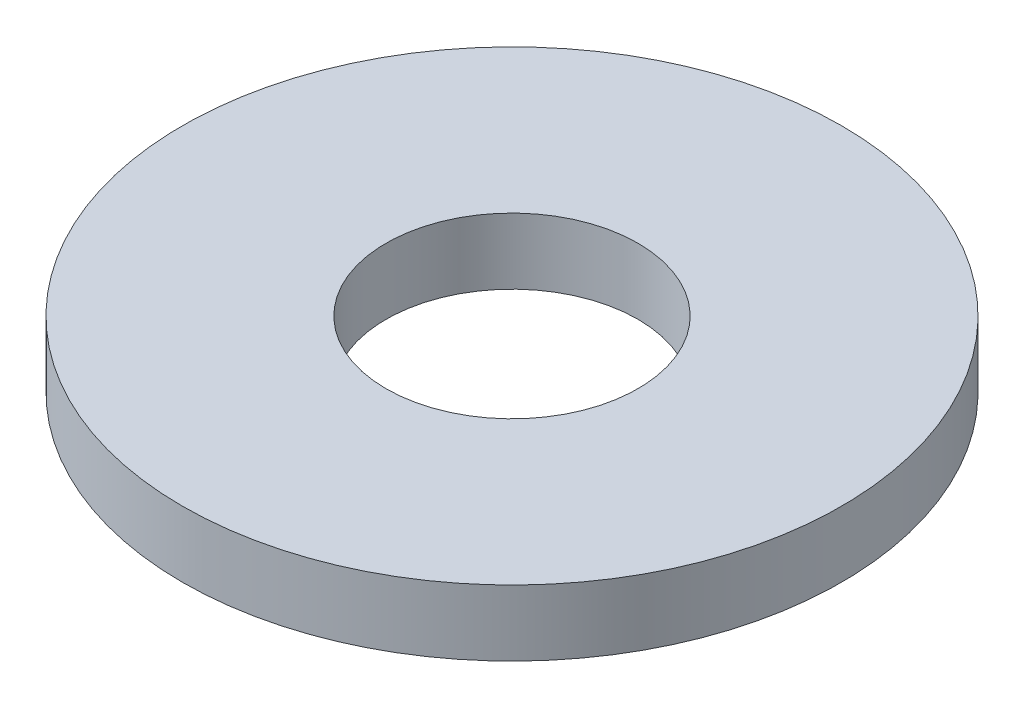
SolidWorks part; units mm, degrees
ref_plane "Front Plane" through (0, 0, 0) normal (0, 0, 1) x (1, 0, 0)
ref_plane "Top Plane" through (0, 0, 0) normal (0, 1, 0) x (1, 0, 0)
ref_plane "Right Plane" through (0, 0, 0) normal (1, 0, 0) x (0, 0, -1)
sketch "Sketch1" plane through (0, 0, 0) normal (0, 1, 0) x (1, 0, 0)
  circle A0 centre (0, 0) radius 85
  dimension "FLANGE_OD" = 170
extrude "Boss-Extrude1" add sketch "Sketch1" along normal blind 17
sketch "Sketch2" plane through (0, 0, 0) normal (0, 1, 0) x (1, 0, 0)
  circle A0 centre (0, 0) radius 32.5
  dimension "BORE_D" = 65
extrude "Cut-Extrude1" cut sketch "Sketch2" along normal through all
sketch "Sketch3" plane through (0, 17, 0) normal (0, 1, 0) x (1, 0, 0)
  circle A0 centre (0, 0) radius 23.581 construction
  circle A1 centre (-23.581, 0) radius 5.4756
  dimension "BOLT_D" = 10.9513
  dimension "BOLT_PCD" = 47.162
extrude "Cut-Extrude2" cut sketch "Sketch3" against normal blind 15.7674 rebuild error yes
pattern_circular "CirPattern1" count 3 over 360 rebuild error yes
